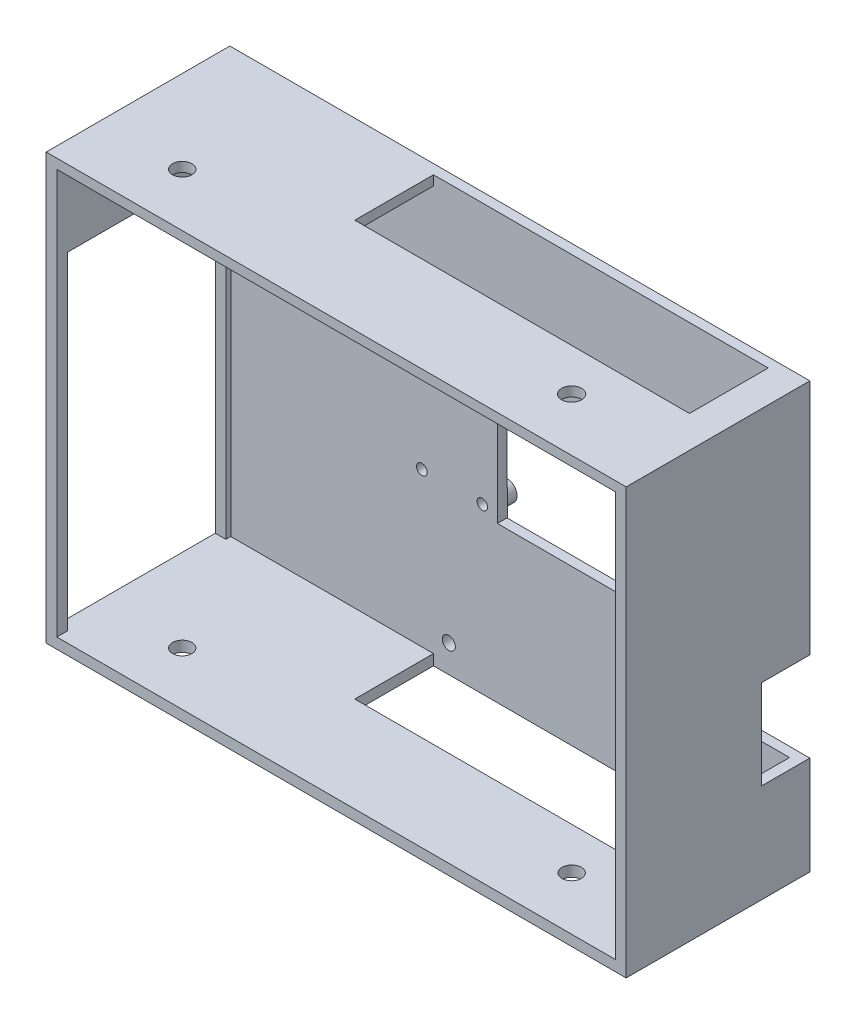
SolidWorks part; units mm, degrees
ref_plane "前视基准面" through (0, 0, 0) normal (0, 0, 1) x (1, 0, 0)
ref_plane "上视基准面" through (0, 0, 0) normal (0, 1, 0) x (1, 0, 0)
ref_plane "右视基准面" through (0, 0, 0) normal (1, 0, 0) x (0, 0, -1)
sketch "草图1" plane through (0, 0, 0) normal (0, 0, 1) x (1, 0, 0)
  line L1 (-523.1068, 343.1867) -> (-403.1068, 343.1867)
  line L2 (-523.1068, 343.1867) -> (-523.1068, 263.1867)
  line L3 (-523.1068, 263.1867) -> (-403.1068, 263.1867)
  line L4 (-403.1068, 343.1867) -> (-403.1068, 263.1867)
  dimension "D1" = 80
  dimension "D2" = 120
extrude "凸台-拉伸1" add sketch "草图1" along normal blind 38
sketch "草图3" plane through (0, 0, 38) normal (0, 0, 1) x (1, 0, 0)
  line L8 (-521.9068, 341.9867) -> (-521.9068, 264.3867)
  line L9 (-521.9068, 264.3867) -> (-404.3068, 264.3867)
  line L10 (-404.3068, 264.3867) -> (-404.3068, 341.9867)
  line L11 (-404.3068, 341.9867) -> (-521.9068, 341.9867)
  line L12 (-521.9068, 341.9867) -> (-521.9068, 264.3867)
  line L13 (-521.9068, 264.3867) -> (-404.3068, 264.3867)
  line L14 (-404.3068, 264.3867) -> (-404.3068, 341.9867)
  line L15 (-404.3068, 341.9867) -> (-521.9068, 341.9867)
  dimension "D1" = 1.2
extrude "切除-拉伸1" cut sketch "草图3" against normal blind 36
sketch "草图4" plane through (0, 0, 0) normal (0, 0, -1) x (-1, 0, 0)
  line L1 (424.5012, 301.0883) -> (399.3482, 301.0883)
  line L2 (424.5012, 301.0883) -> (424.5012, 282.5954)
  line L3 (424.5012, 282.5954) -> (399.3482, 282.5954)
  line L4 (399.3482, 301.0883) -> (399.3482, 282.5954)
extrude "切除-拉伸2" cut sketch "草图4" against normal blind 10
sketch "草图7" plane through (0, 0, 0) normal (0, 0, -1) x (-1, 0, 0)
  line L16 (460.9068, 319.1867) -> (481.5688, 319.1867) construction
  line L17 (465.7551, 319.1867) -> (483.1688, 319.1867)
  line L18 (465.7551, 319.1867) -> (465.7551, 314.1101)
  line L19 (465.7551, 314.1101) -> (483.1688, 314.1101)
  line L20 (483.1688, 319.1867) -> (483.1688, 314.1101)
  line L21 (483.1688, 317.5867) -> (483.1688, 295.7867) construction
  line L22 (481.5688, 294.1867) -> (460.9068, 294.1867) construction
  line L23 (465.7551, 294.1867) -> (483.1688, 294.1867)
  line L24 (465.7551, 294.1867) -> (465.7551, 299.7285)
  line L25 (465.7551, 299.7285) -> (483.1688, 299.7285)
  line L26 (483.1688, 294.1867) -> (483.1688, 299.7285)
extrude "凸台-拉伸2" add sketch "草图7" along normal blind 0.1
ref_plane "基准面1" through (-465.7551, 319.1867, -0.1) normal (0, 0, 1) x (1, 0, 0)
sketch "草图9" plane through (0, 0, 0) normal (0, 0, -1) x (-1, 0, 0)
  line L1 (465.7551, 319.1867) -> (437.8723, 319.1867)
  line L2 (465.7551, 319.1867) -> (465.7551, 294.3082)
  line L3 (465.7551, 294.3082) -> (437.8723, 294.3082)
  line L4 (437.8723, 319.1867) -> (437.8723, 294.3082)
extrude "切除-拉伸4" cut sketch "草图9" against normal blind 12
ref_plane "基准面2" through (0, 303.1867, 0) normal (0, 1, 0) x (1, 0, 0)
sketch "草图12" plane through (0, 0, -0.1) normal (0, 0, -1) x (-1, 0, 0)
  line L1 (467.7688, 318.4867) -> (472.7938, 318.4867)
  line L2 (467.7688, 318.4867) -> (467.7688, 316.2867)
  line L3 (467.7688, 316.2867) -> (472.7938, 316.2867)
  line L4 (472.7938, 318.4867) -> (472.7938, 316.2867)
  line L5 (467.7688, 297.2867) -> (472.7938, 297.2867)
  line L6 (467.7688, 297.2867) -> (467.7688, 295.0867)
  line L7 (467.7688, 295.0867) -> (472.7938, 295.0867)
  line L8 (472.7938, 297.2867) -> (472.7938, 295.0867)
  circle A0 centre (481.3688, 317.3867) radius 1.0852
  circle A1 centre (481.3688, 296.1867) radius 1.1
extrude "切除-拉伸5" cut sketch "草图12" against normal blind 12
sketch "草图13" plane through (0, 0, 2) normal (0, 0, 1) x (1, 0, 0)
  circle A0 centre (-475.8068, 316.8867) radius 1.35
  circle A1 centre (-417.8068, 316.8867) radius 1.35
  circle A2 centre (-417.8068, 267.8867) radius 1.35
  circle A3 centre (-475.8068, 267.8867) radius 1.35
extrude "切除-拉伸6" cut sketch "草图13" against normal blind 12
sketch "草图14" plane through (0, 341.9867, 0) normal (0, -1, 0) x (1, 0, 0)
  line L4 (-404.3068, 38) -> (-521.9068, 38)
  line L5 (-521.9068, 38) -> (-521.9068, 2)
  line L6 (-521.9068, 2) -> (-404.3068, 2)
  line L7 (-404.3068, 2) -> (-404.3068, 38)
  line L8 (-404.3068, 38) -> (-521.9068, 38)
  line L9 (-521.9068, 38) -> (-521.9068, 2)
  line L10 (-521.9068, 2) -> (-404.3068, 2)
  line L11 (-404.3068, 2) -> (-404.3068, 38)
  dimension "D1" = 0
extrude "切除-拉伸7" cut sketch "草图14" against normal blind 10
sketch "草图15" plane through (0, 343.1867, 0) normal (0, 1, 0) x (1, 0, 0)
  line L8 (-521.9068, -2) -> (-404.3068, -2)
  line L9 (-404.3068, -2) -> (-404.3068, -38)
  line L10 (-404.3068, -38) -> (-403.1068, -38)
  line L11 (-403.1068, -38) -> (-403.1068, 0)
  line L12 (-403.1068, 0) -> (-523.1068, 0)
  line L13 (-523.1068, 0) -> (-523.1068, -38)
  line L14 (-523.1068, -38) -> (-521.9068, -38)
  line L15 (-521.9068, -38) -> (-521.9068, -2)
  line L16 (-521.9068, -2) -> (-404.3068, -2)
  line L17 (-404.3068, -2) -> (-404.3068, -38)
  line L18 (-404.3068, -38) -> (-403.1068, -38)
  line L19 (-403.1068, -38) -> (-403.1068, 0)
  line L20 (-403.1068, 0) -> (-523.1068, 0)
  line L21 (-523.1068, 0) -> (-523.1068, -38)
  line L22 (-523.1068, -38) -> (-521.9068, -38)
  line L23 (-521.9068, -38) -> (-521.9068, -2)
  dimension "D1" = 0
extrude "凸台-拉伸3" add sketch "草图15" along normal blind 5
sketch "草图16" plane through (0, 348.1867, 0) normal (0, 1, 0) x (1, 0, 0)
  line L1 (-403.1068, 0) -> (-523.1068, 0)
  line L2 (-403.1068, 0) -> (-403.1068, -38)
  line L3 (-403.1068, -38) -> (-523.1068, -38)
  line L4 (-523.1068, 0) -> (-523.1068, -38)
extrude "凸台-拉伸4" add sketch "草图16" along normal blind 2
sketch "草图17" plane through (-521.9068, 0, 0) normal (1, 0, 0) x (0, 0, -1)
  line L4 (-38, 348.1867) -> (-38, 264.3867)
  line L5 (-38, 264.3867) -> (-2, 264.3867)
  line L6 (-2, 264.3867) -> (-2, 348.1867)
  line L7 (-2, 348.1867) -> (-38, 348.1867)
  line L8 (-38, 348.1867) -> (-38, 264.3867)
  line L9 (-38, 264.3867) -> (-2, 264.3867)
  line L10 (-2, 264.3867) -> (-2, 348.1867)
  line L11 (-2, 348.1867) -> (-38, 348.1867)
  dimension "D1" = 0
extrude "凸台-拉伸5" add sketch "草图17" along normal blind 1
sketch "草图18" plane through (-404.3068, 0, 0) normal (-1, 0, 0) x (0, 0, 1)
  line L8 (10, 301.0883) -> (10, 282.5954)
  line L9 (10, 282.5954) -> (2, 282.5954)
  line L10 (2, 282.5954) -> (2, 264.3867)
  line L11 (2, 264.3867) -> (38, 264.3867)
  line L12 (38, 264.3867) -> (38, 348.1867)
  line L13 (38, 348.1867) -> (2, 348.1867)
  line L14 (2, 348.1867) -> (2, 301.0883)
  line L15 (2, 301.0883) -> (10, 301.0883)
  line L16 (10, 301.0883) -> (10, 282.5954)
  line L17 (10, 282.5954) -> (2, 282.5954)
  line L18 (2, 282.5954) -> (2, 264.3867)
  line L19 (2, 264.3867) -> (38, 264.3867)
  line L20 (38, 264.3867) -> (38, 348.1867)
  line L21 (38, 348.1867) -> (2, 348.1867)
  line L22 (2, 348.1867) -> (2, 301.0883)
  line L23 (2, 301.0883) -> (10, 301.0883)
  dimension "D1" = 0
extrude "凸台-拉伸6" add sketch "草图18" along normal blind 1
sketch "草图19" plane through (0, 263.1867, 0) normal (0, -1, 0) x (1, 0, 0)
  line L4 (-523.1068, 0) -> (-403.1068, 0)
  line L5 (-403.1068, 0) -> (-403.1068, 38)
  line L6 (-403.1068, 38) -> (-523.1068, 38)
  line L7 (-523.1068, 38) -> (-523.1068, 0)
  line L8 (-523.1068, 0) -> (-403.1068, 0)
  line L9 (-403.1068, 0) -> (-403.1068, 38)
  line L10 (-403.1068, 38) -> (-523.1068, 38)
  line L11 (-523.1068, 38) -> (-523.1068, 0)
  dimension "D1" = 0
extrude "凸台-拉伸7" add sketch "草图19" along normal blind 1
ref_plane "基准面3" through (-467.7688, 0, 0) normal (-1, 0, 0) x (0, 0, 1)
sketch "草图21" plane through (0, 0, -0.1) normal (0, 0, -1) x (-1, 0, 0)
  line L0 (467.7688, 318.4867) -> (467.7688, 316.2867) construction
  line L1 (467.7688, 316.2867) -> (472.7938, 316.2867) construction
  line L2 (472.7938, 316.2867) -> (472.7938, 318.4867) construction
  line L3 (472.7938, 318.4867) -> (467.7688, 318.4867) construction
  line L4 (467.7688, 318.4867) -> (467.7688, 316.2867)
  line L5 (467.7688, 316.2867) -> (472.7938, 316.2867)
  line L6 (472.7938, 316.2867) -> (472.7938, 318.4867)
  line L7 (472.7938, 318.4867) -> (467.7688, 318.4867)
  line L8 (467.7688, 297.2867) -> (467.7688, 295.0867) construction
  line L9 (467.7688, 295.0867) -> (472.7938, 295.0867) construction
  line L10 (472.7938, 295.0867) -> (472.7938, 297.2867) construction
  line L11 (472.7938, 297.2867) -> (467.7688, 297.2867) construction
  line L12 (467.7688, 297.2867) -> (467.7688, 295.0867)
  line L13 (467.7688, 295.0867) -> (472.7938, 295.0867)
  line L14 (472.7938, 295.0867) -> (472.7938, 297.2867)
  line L15 (472.7938, 297.2867) -> (467.7688, 297.2867)
extrude "凸台-拉伸9" add sketch "草图21" against normal up to surface (2.1 mm away) up to face at (-474.4568, 267.8867, 2)
sketch "草图22" plane through (0, 0, -0.1) normal (0, 0, -1) x (-1, 0, 0)
  circle A2 centre (468.8648, 317.3867) radius 1.0852
  circle A3 centre (468.8648, 296.1867) radius 1.0852
extrude "切除-拉伸8" cut sketch "草图22" against normal blind 10
sketch "草图23" plane through (0, 0, -0.1) normal (0, 0, -1) x (-1, 0, 0)
  circle A0 centre (481.3688, 317.3867) radius 2.0852
  circle A1 centre (481.3688, 317.3867) radius 1.0852 construction
  circle A2 centre (468.8648, 317.3867) radius 2.0852
  circle A3 centre (481.3688, 296.1867) radius 2.0852
  circle A4 centre (468.8648, 296.1867) radius 2.0852
  circle A5 centre (481.3688, 317.3867) radius 1.0852
  circle A6 centre (468.8648, 317.3867) radius 1.0852 construction
  circle A7 centre (468.8648, 317.3867) radius 1.0852
  circle A8 centre (468.8648, 296.1867) radius 1.0852 construction
  circle A9 centre (468.8648, 296.1867) radius 1.0852
  circle A10 centre (481.3688, 296.1867) radius 1.1 construction
  circle A11 centre (481.3688, 296.1867) radius 1.1
  dimension "D1" = 1
extrude "凸台-拉伸10" add sketch "草图23" along normal blind 3
ref_plane "基准面4" through (-403.1068, 301.0883, 0) normal (0, 1, 0) x (1, 0, 0)
ref_plane "基准面5" through (0, 306.1867, 0) normal (0, 1, 0) x (1, 0, 0)
ref_plane "基准面6" through (-463.1068, 0, 0) normal (-1, 0, 0) x (0, 0, 1)
ref_plane "基准面7" through (0, 0, 19) normal (0, 0, 1) x (1, 0, 0)
sketch "草图26" plane through (0, 350.1867, 0) normal (0, 1, 0) x (1, 0, 0)
  line L0 (-520.9068, -2) -> (-405.3068, -2) construction
  line L1 (-478.9691, -2) -> (-409.717, -2)
  line L2 (-478.9691, -2) -> (-478.9691, -18.2904)
  line L3 (-478.9691, -18.2904) -> (-409.717, -18.2904)
  line L4 (-409.717, -2) -> (-409.717, -18.2904)
extrude "切除-拉伸9" cut sketch "草图26" against normal blind 10
sketch "草图29" plane through (-523.1068, 0, 0) normal (-1, 0, 0) x (0, 0, 1)
  line L0 (38, 264.3867) -> (2, 264.3867) construction
  line L1 (3.0054, 332.2192) -> (25.6265, 332.2192)
  line L2 (3.0054, 332.2192) -> (3.0054, 264.3867)
  line L3 (3.0054, 264.3867) -> (25.6265, 264.3867)
  line L4 (25.6265, 332.2192) -> (25.6265, 264.3867)
extrude "切除-拉伸10" cut sketch "草图29" against normal blind 10
sketch "草图30" plane through (0, 262.1867, 0) normal (0, -1, 0) x (1, 0, 0)
  line L0 (-520.9068, 2) -> (-405.3068, 2) construction
  line L1 (-478.9691, 18.2904) -> (-410.7599, 18.2904)
  line L2 (-478.9691, 18.2904) -> (-478.9691, 2)
  line L3 (-478.9691, 2) -> (-410.7599, 2)
  line L4 (-410.7599, 18.2904) -> (-410.7599, 2)
extrude "切除-拉伸11" cut sketch "草图30" against normal blind 10
ref_plane "基准面8" through (-523.1068, 264.3867, 3.0054) normal (0, -1, 0) x (-1, 0, 0)
sketch "草图31" plane through (-523.1068, 264.3867, 3.0054) normal (0, -1, 0) x (1, 0, 0)
  line L0 (112.3469, 15.285) -> (44.1377, 15.285) construction
  line L1 (110.8964, 15.285) -> (116.2078, 15.285)
  line L2 (110.8964, 15.285) -> (110.8964, -1.0054)
  line L3 (110.8964, -1.0054) -> (116.2078, -1.0054)
  line L4 (116.2078, 15.285) -> (116.2078, -1.0054)
  line L5 (112.3469, -1.0054) -> (117.8, -1.0054) construction
extrude "切除-拉伸14" cut sketch "草图31" along normal blind 9
sketch "草图32" plane through (0, 262.1867, 0) normal (0, -1, 0) x (1, 0, 0)
  circle A0 centre (-505.9528, 27) radius 2
  circle A1 centre (-425.3802, 27) radius 2
  dimension "D1" = 4
extrude "切除-拉伸15" cut sketch "草图32" against normal blind 9
sketch "草图33" plane through (0, 350.1867, 0) normal (0, 1, 0) x (1, 0, 0)
  circle A0 centre (-505.9528, -27) radius 2
  circle A1 centre (-425.3802, -27) radius 2.0652
extrude "切除-拉伸16" cut sketch "草图33" against normal blind 9
sketch "草图34" plane through (-523.1068, 0, 0) normal (-1, 0, 0) x (0, 0, 1)
  line L0 (32, 264.3867) -> (38, 264.3867) construction
  line L1 (25.6265, 332.2192) -> (35.8228, 332.2192)
  line L2 (25.6265, 332.2192) -> (25.6265, 264.3867)
  line L3 (25.6265, 264.3867) -> (35.8228, 264.3867)
  line L4 (35.8228, 332.2192) -> (35.8228, 264.3867)
extrude "切除-拉伸17" cut sketch "草图34" against normal blind 9
sketch "草图20" plane through (0, 0, -0.1) normal (0, 0, -1) x (-1, 0, 0)
  circle A0 centre (481.3688, 317.3867) radius 2
  circle A1 centre (481.3688, 296.1867) radius 1.1 construction
  circle A2 centre (481.3688, 296.1867) radius 2.0016
  circle A3 centre (481.3688, 317.3867) radius 1.0852 construction
  circle A4 centre (481.3688, 296.1867) radius 1.1
  circle A5 centre (481.3688, 317.3867) radius 1.0852
  dimension "D1" = 4
extrude "凸台-拉伸8" add sketch "草图20" along normal blind 2
